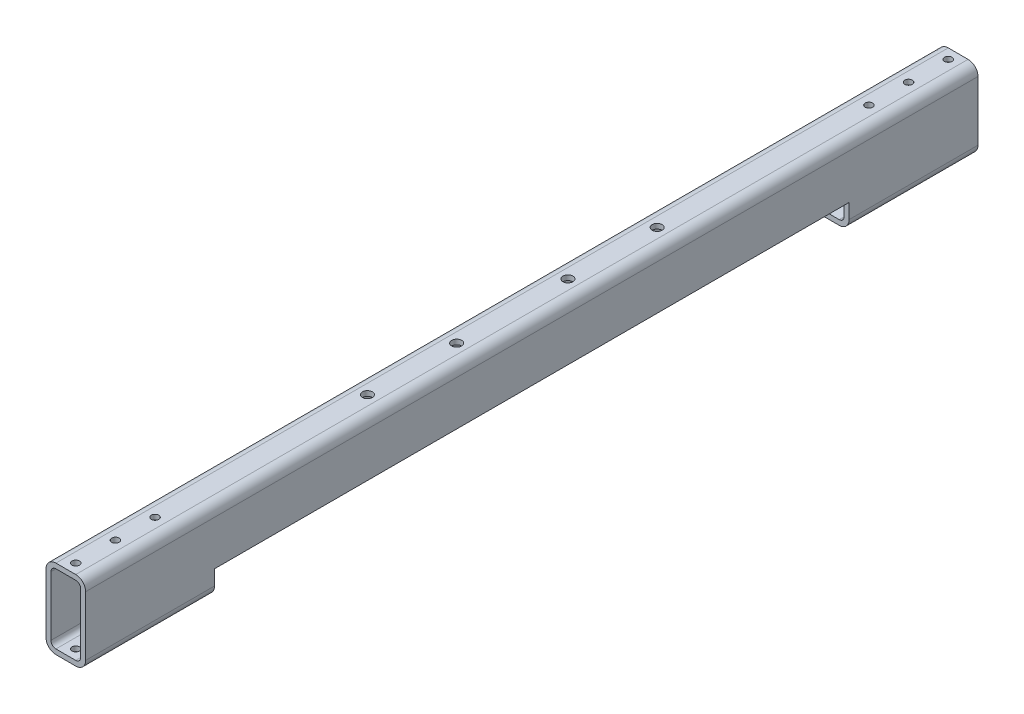
SolidWorks part; units mm, degrees
material "6061-T6 (SS)"
ref_plane "Front Plane" through (0, 0, 0) normal (0, 0, 1) x (1, 0, 0)
ref_plane "Top Plane" through (0, 0, 0) normal (0, 1, 0) x (1, 0, 0)
ref_plane "Right Plane" through (0, 0, 0) normal (1, 0, 0) x (0, 0, -1)
sketch "Sketch1" plane through (0, 0, 0) normal (0, 0, 1) x (1, 0, 0)
  line L1 (-6.35, -25.4) -> (6.35, -25.4)
  line L2 (-12.7, -19.05) -> (-12.7, 19.05)
  line L3 (-6.35, 25.4) -> (6.35, 25.4)
  line L4 (12.7, -19.05) -> (12.7, 19.05)
  line L5 (-12.7, -25.4) -> (12.7, 25.4) construction
  line L6 (-12.7, 25.4) -> (12.7, -25.4) construction
  arc A0 (-12.7, -19.05) -> (-6.35, -25.4) centre (-6.35, -19.05) ccw
  arc A1 (6.35, -25.4) -> (12.7, -19.05) centre (6.35, -19.05) ccw
  arc A2 (6.35, 25.4) -> (12.7, 19.05) centre (6.35, 19.05) cw
  arc A3 (-12.7, 19.05) -> (-6.35, 25.4) centre (-6.35, 19.05) cw
  point P0 (0, 0)
  dimension "D3" = 6.35
  dimension "D1" = 50.8
  dimension "D2" = 25.4
extrude "Extrude-Thin1" add sketch "Sketch1" along normal blind 571.5 thin thin type one direction reverse wall 3.175
hole_wizard "3/16 (0.1875) Diameter Hole1" positions "3DSketch1" profile "Sketch3" hole size "3/16" standard "ANSI Inch" end condition through all
sketch3d "3DSketch1"
  line L1 (6.35, 25.4, 0) -> (-6.35, 25.4, 0) construction
  line L6 (0, 25.4, 571.5) -> (0, 25.4, 0) construction
  line L7 (6.35, 25.4, 571.5) -> (-6.35, 25.4, 571.5) construction
  point P57 (0, 25.4, 6.35)
  point P59 (0, 25.4, 31.75)
  point P61 (0, 25.4, 57.15)
  point P63 (0, 25.4, 539.75)
  point P65 (0, 25.4, 514.35)
  point P67 (0, 25.4, 565.15)
  dimension "D1" = 25.4
  dimension "D2" = 25.4
  dimension "D3" = 6.35
  dimension "D4" = 25.4
  dimension "D5" = 25.4
  dimension "D6" = 6.35
sketch "Sketch3" plane through (0, 25.4, 565.15) normal (1, 0, 0) x (0, 0, 1)
  line L0 (0, 0) -> (0, 50.8)
  line L1 (0, 50.8) -> (2.3812, 50.8)
  line L2 (2.3812, 50.8) -> (2.3812, 0)
  line L5 (2.3812, 0) -> (0, 0)
  line L11 (0, -6.35) -> (0, 107.95) construction
  dimension "Thru Hole Dia." = 4.7625
  dimension "Thru Hole Depth" = 50.8
sketch "Sketch5" plane through (12.7, 0, 0) normal (1, 0, 0) x (0, 0, -1)
  line L0 (-488.95, -9.525) -> (-488.95, -25.4)
  line L2 (-488.95, -25.4) -> (-82.55, -25.4)
  line L3 (-82.55, -25.4) -> (-82.55, -9.525)
  line L4 (-82.55, -9.525) -> (-488.95, -9.525)
  line L12 (-571.5, -25.4) -> (0, -25.4) construction
  point P11 (-285.75, -25.4)
  point P12 (-285.75, -25.4)
  dimension "D1" = 15.875
  dimension "D2" = 406.4
extrude "Cut-Extrude1" cut sketch "Sketch5" against normal through all
hole_wizard "1/4 (0.25) Diameter Hole1" positions "Sketch6" profile "Sketch7" hole size "1/4" standard "ANSI Inch" end condition through all
sketch "Sketch6" plane through (0, 25.4, 0) normal (0, 1, 0) x (1, 0, 0)
  point P0 (0, -321.183)
  point P3 (0, -378.333)
  point P6 (0, -192.786)
  point P9 (0, -249.936)
sketch "Sketch7" plane through (0, 25.4, 321.183) normal (1, 0, 0) x (0, 0, 1)
  line L0 (0, 0) -> (0, 50.8)
  line L1 (0, 50.8) -> (3.175, 50.8)
  line L2 (3.175, 50.8) -> (3.175, 0)
  line L5 (3.175, 0) -> (0, 0)
  line L11 (0, -6.35) -> (0, 107.95) construction
  dimension "Thru Hole Dia." = 6.35
  dimension "Thru Hole Depth" = 50.8
hole_wizard "E (0.25) Diameter Hole1" positions "Sketch8" profile "Sketch9" hole size "E" standard "ANSI Inch"
sketch "Sketch8" plane through (-12.7, 0, 0) normal (-1, 0, 0) x (0, 0, 1)
  point P0 (103.886, 17.145)
  point P3 (103.886, 1.27)
  point P6 (116.586, 8.89)
  point P13 (454.914, 8.89)
  point P16 (467.614, 1.27)
  point P19 (467.614, 17.145)
sketch "Sketch9" plane through (-12.7, 17.145, 103.886) normal (0, 1, 0) x (0, 0, 1)
  line L0 (0, 0) -> (0, 8.2577)
  line L1 (0, 8.2577) -> (3.175, 6.35)
  line L2 (3.175, 6.35) -> (3.175, 0)
  line L5 (3.175, 0) -> (0, 0)
  line L10 (0, 8.2577) -> (-3.175, 6.35) construction
  line L11 (0, -6.35) -> (0, 107.95) construction
  dimension "Hole Dia." = 6.35
  dimension "Hole Depth" = 6.35
  dimension "Drill Angle" = 118
